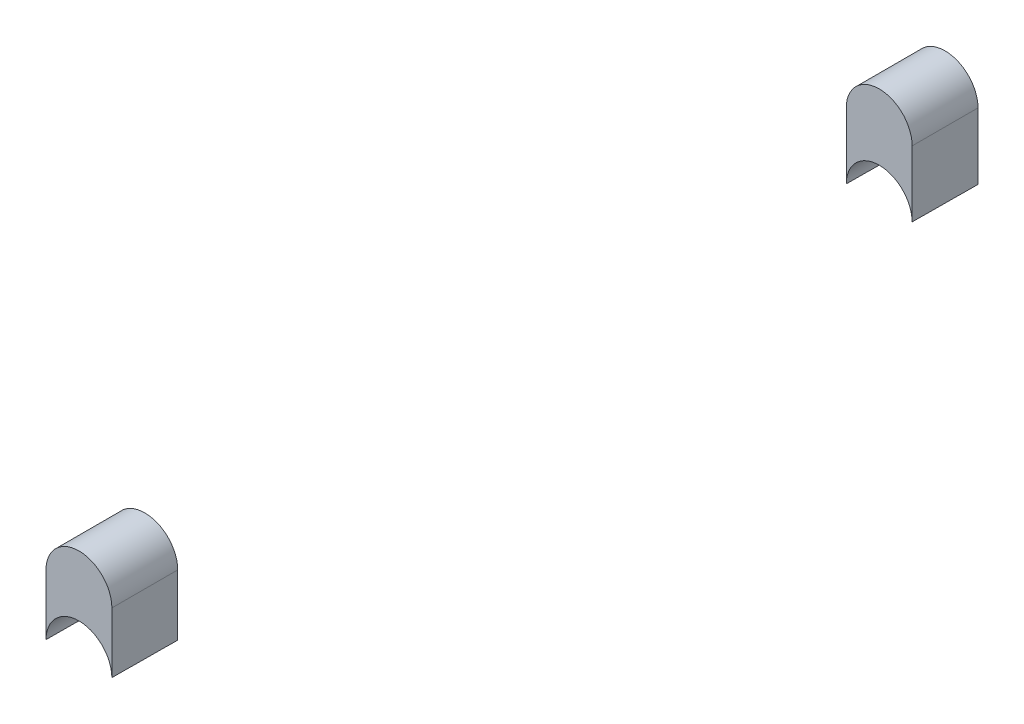
SolidWorks part; units mm, degrees
ref_plane "Front Plane" through (0, 0, 0) normal (0, 0, 1) x (1, 0, 0)
ref_plane "Top Plane" through (0, 0, 0) normal (0, 1, 0) x (1, 0, 0)
ref_plane "Right Plane" through (0, 0, 0) normal (1, 0, 0) x (0, 0, -1)
sketch "Sketch2" plane through (0, 0, 0) normal (0, 0, 1) x (1, 0, 0)
  line L1 (0, -50) -> (0, 50) construction
  line L3 (-5, -50) -> (-5, 50)
  line L4 (5, -50) -> (5, 50)
  line L5 (-5, -50) -> (-5, 50)
  line L6 (5, -50) -> (5, 50)
  circle A0 centre (0, 50) radius 5
  circle A1 centre (0, -50) radius 5
  point P13 (0, 0)
  dimension "D1" = 10
  dimension "D2" = 100
extrude "Boss-Extrude2" add sketch "Sketch2" along normal blind 65.75 and the other way blind 65.75 contours A0 | L1 A1 L4 A0 | A1 L1 A0 L3 region at (-2.5322, 0, 0) region at (2.5322, 0, 0) region at (-3.4355, 46.5645, 0)
sketch "Sketch3" plane through (0, 0, 0) normal (1, 0, 0) x (0, 0, -1)
  line L0 (-70.4541, 40.8321) -> (70.387, 39.8681) construction
  line L3 (-65.75, 45.8) -> (65.75, 44.9)
  line L4 (-65.75, -50) -> (-65.75, 50) construction
  line L5 (65.75, -50) -> (65.75, 50) construction
  line L6 (-65.75, 45.8) -> (-65.75, 55) construction
  line L7 (65.75, 44.9) -> (65.75, 55) construction
  line L8 (-65.75, 45.8) -> (-65.75, 40.7999)
  line L9 (-65.75, 40.7999) -> (65.75, 39.8999)
  line L10 (65.75, 39.8999) -> (65.75, 44.9)
  dimension "D1" = 9.2
  dimension "D2" = 10.1
  dimension "D3" = 5
sketch "Sketch5" plane through (0, 0, 65.75) normal (0, 0, 1) x (1, 0, 0)
  line L0 (-5.0001, 40.7999) -> (-5, -50)
  line L1 (-5, -50) -> (-5, 50) construction
  line L2 (-5, -50) -> (5, -50)
  line L3 (5, -50) -> (5.0001, 40.7999)
  circle A0 centre (0, 40.7999) radius 5.0001
  arc A1 (5, -50) -> (-5, -50) centre (0, -50) ccw construction
  line M3 (-5, 50) -> (-5, -50)
  arc M4 (-5, -50) -> (5, -50) centre (0, -50) cw
  line M5 (5, -50) -> (5, 50)
extrude "Cut-Extrude1" cut sketch "Sketch5" along direction (0, -0.0068, -1) on the side against the normal through all contours A0 M5 M3 | A0 M3 M4 M5 region at (0, -4.6002, 65.75) region at (0, 40.7999, 65.75)
sketch "Sketch6" plane through (0, 0, 0) normal (1, 0, 0) x (0, 0, -1)
  line L0 (-65.75, 40.8341) -> (-65.75, 50) construction
  line L1 (-55.75, 55) -> (55.75, 55)
  line L2 (-55.75, 55) -> (-55.75, 35)
  line L3 (-55.75, 35) -> (55.75, 35)
  line L4 (55.75, 55) -> (55.75, 35)
  line L5 (65.75, 39.9341) -> (65.75, 50) construction
  line L6 (65.75, 55) -> (-65.75, 55) construction
  point P10 (0, 0)
  dimension "D1" = 10
  dimension "D2" = 10
  dimension "D3" = 20
extrude "Cut-Extrude2" cut sketch "Sketch6" against normal through all both and the other way through all
